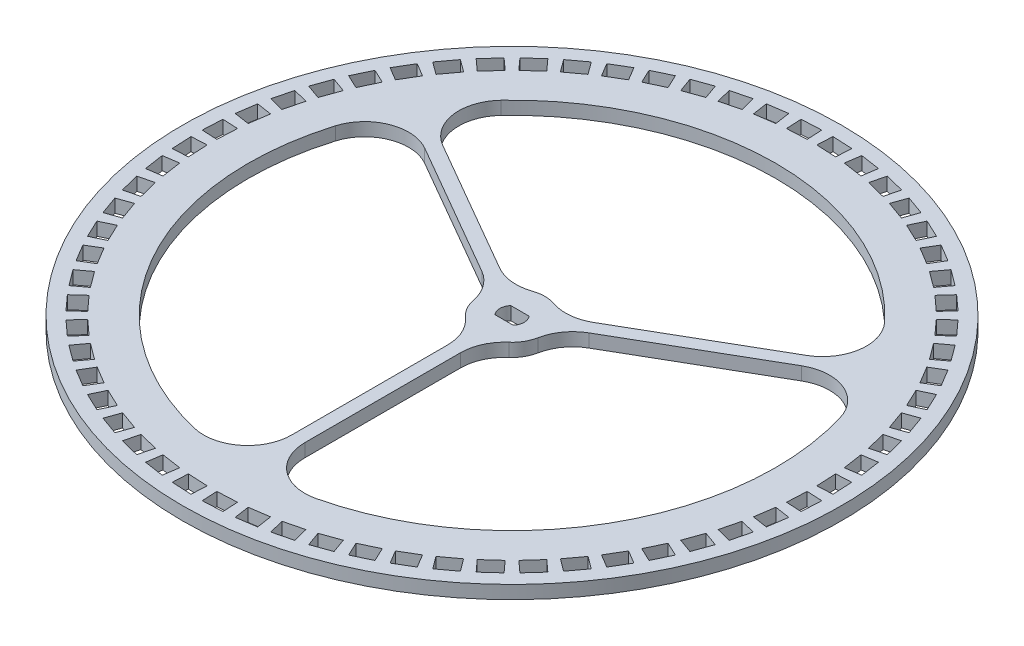
SolidWorks part; units mm, degrees
ref_plane "前视基准面" through (0, 0, 0) normal (0, 0, 1) x (1, 0, 0)
ref_plane "上视基准面" through (0, 0, 0) normal (0, 1, 0) x (1, 0, 0)
ref_plane "右视基准面" through (0, 0, 0) normal (1, 0, 0) x (0, 0, -1)
sketch "Sketch4" plane through (0, 0, 0) normal (0, 1, 0) x (1, 0, 0)
  line L0 (60, 0) -> (75, 0)
  line L1 (59.7111, 5.881) -> (74.6389, 7.3513)
  line L2 (0, 0) -> (74.9097, 3.6801) construction
  line L3 (68.0574, 5.5962) -> (71.5532, 5.7679)
  line L4 (71.5532, 5.7679) -> (71.774, 1.2733)
  line L5 (71.774, 1.2733) -> (68.2782, 1.1016)
  line L6 (68.2782, 1.1016) -> (68.0574, 5.5962)
  line L7 (68.0574, 5.5962) -> (71.774, 1.2733) construction
  line L8 (59.7111, 5.881) -> (0, 0) construction
  line L9 (0, 0) -> (60, 0) construction
  arc A0 (75, 0) -> (74.6389, 7.3513) centre (0, 0) ccw
  arc A1 (59.7111, 5.881) -> (60, 0) centre (0, 0) cw
  point P9 (69.9157, 3.4347)
  dimension "D1" = 5
  dimension "D5" = 75
  dimension "D6" = 60
  dimension "D2" = 3.5
  dimension "D3" = 4.5
  dimension "D4" = 5.625
extrude "Boss-Extrude3" add sketch "Sketch4" along normal blind 3
pattern_circular "CirPattern1" count 64 over 360 about axis through (0, 0, 0) along (0, 1, 0) of "Boss-Extrude3"
sketch "Sketch5" plane through (0, 0, 0) normal (0, -1, 0) x (1, 0, 0)
  line L0 (2.0791, 1.8) -> (-2.0791, 1.8)
  line L1 (2.0791, -1.8) -> (-2.0791, -1.8)
  circle A0 centre (0, 0) radius 7.5
  circle A1 centre (0, 0) radius 2.75 construction
  arc A2 (-2.0791, 1.8) -> (-2.0791, -1.8) centre (0, 0) ccw
  arc A3 (2.0791, 1.8) -> (2.0791, -1.8) centre (0, 0) cw
  dimension "D1" = 15
  dimension "D2" = 1.8
  dimension "D3" = 5.5
extrude "Boss-Extrude4" add sketch "Sketch5" against normal up to surface (3 mm away) separate body contours A0 region at (-7.2879, 0, 0) up to face at (0, 3, -60)
sketch "Sketch7" plane through (0, 0, 0) normal (0, -1, 0) x (1, 0, 0)
  line L0 (0, 6.8) -> (0, 60) construction
  line L2 (-1.5, 6.8) -> (-1.5, 60)
  line L3 (-1.5, 6.8) -> (1.5, 6.8)
  line L4 (-1.5, 60) -> (1.5, 60)
  line L5 (1.5, 6.8) -> (1.5, 60)
  line L6 (-1.5, 6.8) -> (1.5, 60) construction
  line L7 (-1.5, 60) -> (1.5, 6.8) construction
  line L8 (2.0791, 1.8) -> (-2.0791, 1.8) construction
  circle A0 centre (0, 0) radius 60 construction
  point P8 (0, 33.4)
  dimension "D1" = 3
  dimension "D2" = 5
extrude "Boss-Extrude5" add sketch "Sketch7" against normal up to surface (3 mm away) up to face at (0, 3, -60)
fillet "Fillet1" radius 10 4 edges at (1.5, 1.5, 7.3485) (-1.5, 1.5, 7.3485) (1.5, 1.5, 59.9812) (-1.5, 1.5, 59.9812)
pattern_circular "CirPattern2" count 3 over 360 about axis through (0, 0, 0) along (0, -1, 0) of "Boss-Extrude5", "Fillet1"
